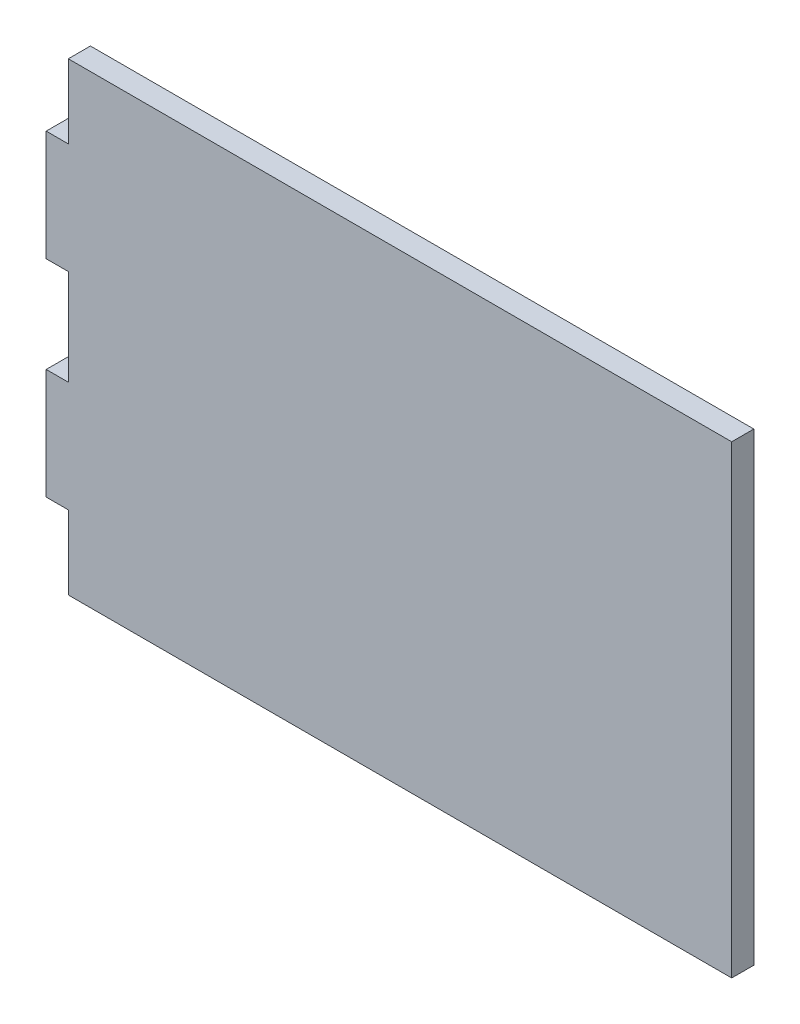
SolidWorks part; units mm, degrees
ref_plane "Front Plane" through (0, 0, 0) normal (0, 0, 1) x (1, 0, 0)
ref_plane "Top Plane" through (0, 0, 0) normal (0, 1, 0) x (1, 0, 0)
ref_plane "Right Plane" through (0, 0, 0) normal (1, 0, 0) x (0, 0, -1)
sketch "Sketch1" plane through (0, 0, 0) normal (0, 0, 1) x (1, 0, 0)
  line L0 (-45, 0) -> (45, 0) construction
  line L1 (-45, -31.5) -> (45, -31.5)
  line L2 (-45, -31.5) -> (-45, 31.5)
  line L3 (-45, 31.5) -> (45, 31.5)
  line L4 (45, -31.5) -> (45, 31.5)
  line L5 (-45, -31.5) -> (45, 31.5) construction
  line L6 (-45, 31.5) -> (45, -31.5) construction
  line L7 (-45, -6.5) -> (-48, -6.5)
  line L8 (-45, 21.5) -> (-48, 21.5)
  line L9 (-45, 21.5) -> (-45, 6.5)
  line L10 (-45, 6.5) -> (-48, 6.5)
  line L11 (-48, 21.5) -> (-48, 6.5)
  line L16 (-48, -21.5) -> (-48, -6.5)
  line L17 (-45, -21.5) -> (-48, -21.5)
  line L18 (-45, -21.5) -> (-45, -6.5)
  point P0 (0, 0)
  dimension "D1" = 90
  dimension "D2" = 63
  dimension "D3" = 15
  dimension "D4" = 13
  dimension "D5" = 3
extrude "Boss-Extrude1" add sketch "Sketch1" along normal mid plane 3 contours L1 L4 L3 L2 | L8 L11 L10 L2 | L17 L2 L7 L16 region at (0, 0, 0) region at (-46.5, -14, 0) region at (-46.5, 14, 0)
